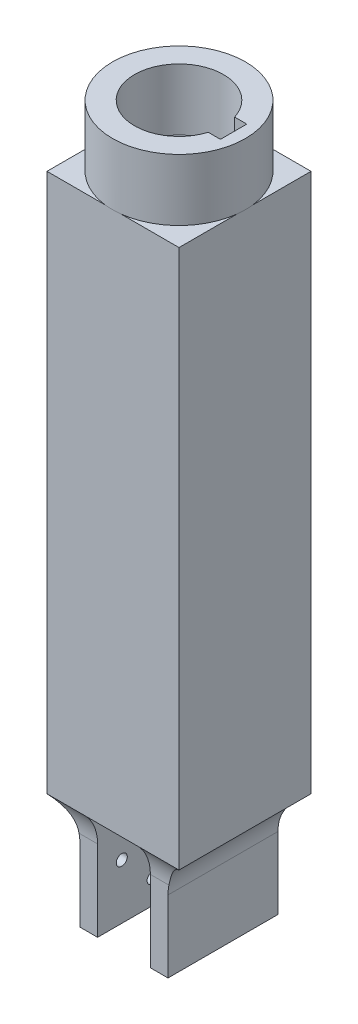
SolidWorks part; units mm, degrees
ref_plane "Front Plane" through (0, 0, 0) normal (0, 0, 1) x (1, 0, 0)
ref_plane "Top Plane" through (0, 0, 0) normal (0, 1, 0) x (1, 0, 0)
ref_plane "Right Plane" through (0, 0, 0) normal (1, 0, 0) x (0, 0, -1)
sketch "Sketch1" plane through (0, 0, 0) normal (0, 1, 0) x (1, 0, 0)
  line L1 (-15, -15) -> (15, -15)
  line L2 (-15, -15) -> (-15, 15)
  line L3 (-15, 15) -> (15, 15)
  line L4 (15, -15) -> (15, 15)
  line L5 (-15, -15) -> (15, 15) construction
  line L6 (-15, 15) -> (15, -15) construction
  point P0 (0, 0)
  dimension "D1" = 30
  dimension "D2" = 30
extrude "Boss-Extrude1" add sketch "Sketch1" along normal blind 122.5
sketch "Sketch2" plane through (0, 0, 0) normal (0, -1, 0) x (1, 0, 0)
  line L0 (-15, 15) -> (15, 15) construction
  line L1 (0, 0) -> (0, 15) construction
  line L6 (-15, -15) -> (-15, 15) construction
  line L7 (6, -12.5) -> (10, 12.5) construction
  line L8 (-6, 12.5) -> (-10, -12.5) construction
  line L9 (-6, -12.5) -> (-10, 12.5) construction
  line L10 (-10, -12.5) -> (-10, 12.5)
  line L11 (-6, 12.5) -> (-10, 12.5)
  line L12 (-6, -12.5) -> (-6, 12.5)
  line L13 (-6, -12.5) -> (-10, -12.5)
  line L14 (6, 12.5) -> (10, -12.5) construction
  line L15 (6, -12.5) -> (10, -12.5)
  line L16 (6, -12.5) -> (6, 12.5)
  line L17 (6, 12.5) -> (10, 12.5)
  line L18 (10, -12.5) -> (10, 12.5)
  point P15 (8, 0)
  point P23 (-8, 0)
  dimension "D1" = 4
  dimension "D2" = 25
  dimension "D4" = 5
  dimension "D5" = 2.5
extrude "Boss-Extrude2" add sketch "Sketch2" along normal blind 25
sketch "Sketch3" plane through (0, 122.5, 0) normal (0, 1, 0) x (1, 0, 0)
  line L8 (12, -12) -> (12, 12)
  line L9 (12, 12) -> (-12, 12)
  line L10 (-12, 12) -> (-12, -12)
  line L11 (-12, -12) -> (12, -12)
  line L12 (12, -12) -> (12, 12)
  line L13 (12, 12) -> (-12, 12)
  line L14 (-12, 12) -> (-12, -12)
  line L15 (-12, -12) -> (12, -12)
  dimension "D1" = 3
extrude "Cut-Extrude1" cut sketch "Sketch3" against normal blind 110
sketch "Sketch5" plane through (0, 122.5, 0) normal (0, 1, 0) x (1, 0, 0)
  line L5 (-15, -15) -> (15, 15) construction
  line L6 (-15, 15) -> (15, -15) construction
  line L11 (-12, -12) -> (12, -12)
  line L12 (-12, -12) -> (-12, 12)
  line L13 (-12, 12) -> (12, 12)
  line L14 (12, -12) -> (12, 12)
  line L15 (-12, -12) -> (12, 12) construction
  line L16 (-12, 12) -> (12, -12) construction
  point P0 (0, 0)
  point P7 (0, 0)
extrude "Boss-Extrude4" add sketch "Sketch5" against normal blind 4
sketch "Sketch4" plane through (0, 122.5, 0) normal (0, 1, 0) x (1, 0, 0)
  line L1 (12.4127, -2.9969) -> (12.4127, 2.9969)
  line L2 (12.4127, 2.9969) -> (9.6451, 2.9969)
  line L4 (12.4127, -2.9969) -> (9.6451, -2.9969)
  circle A1 centre (0, 0) radius 15.1
  arc A2 (9.6451, 2.9969) -> (9.6451, -2.9969) centre (0, 0) ccw
  point P7 (12.4127, 0)
  dimension "D1" = 20.2
  dimension "D2" = 5.9938
extrude "Boss-Extrude3" add sketch "Sketch4" along normal blind 14
sketch "Sketch7" plane through (0, 122.5, 0) normal (0, 1, 0) x (1, 0, 0)
  line L4 (12.4127, 2.9969) -> (12.4127, -2.9969)
  line L5 (12.4127, -2.9969) -> (9.6451, -2.9969)
  line L6 (9.6451, -2.9969) -> (9.6451, 2.9969)
  line L7 (9.6451, 2.9969) -> (12.4127, 2.9969)
extrude "Cut-Extrude3" cut sketch "Sketch7" against normal blind 4
sketch "Sketch8" plane through (-10, 0, 0) normal (-1, 0, 0) x (0, 0, 1)
  line L0 (-12.5, -25) -> (-12.5, 0) construction
  line L1 (12.5, -25) -> (-12.5, -25) construction
  circle A0 centre (0, -12.5) radius 7 construction
  circle A1 centre (0, -5.5) radius 1.25
  circle A2 centre (7, -12.5) radius 1.25
  circle A3 centre (0, -19.5) radius 1.25
  circle A4 centre (-7, -12.5) radius 1.25
  circle A5 centre (0, -12.5) radius 1.5
  point P13 (0, -12.5)
  dimension "D1" = 14
  dimension "D2" = 2.5
  dimension "D4" = 14
  dimension "D5" = 7
  dimension "D6" = 12.5
  dimension "D7" = 12.5
  dimension "D8" = 3
  dimension "D3" = 4
sketch "Sketch12" plane through (0, 122.5, 0) normal (0, 1, 0) x (1, 0, 0)
  circle A0 centre (0, 0) radius 2.1
  dimension "D1" = 4.2
extrude "Cut-Extrude6" cut sketch "Sketch12" against normal through all
sketch "Sketch13" plane through (0, 0, 0) normal (0, -1, 0) x (1, 0, 0)
  line L0 (-4.5, 11) -> (4.5, 11)
  line L1 (4.5, 11) -> (4.5, -11)
  line L2 (4.5, -11) -> (-4.5, -11)
  line L3 (-4.5, -11) -> (-4.5, 11)
  point P3 (0, 11)
  point P6 (4.5, 0)
  dimension "D1" = 9
  dimension "D2" = 22
extrude "Cut-Extrude7" cut sketch "Sketch13" against normal blind 20
extrude "Cut-Extrude4" cut sketch "Sketch8" against normal blind 4
fillet "Fillet1" radius 10 6 edges at (-8, 0, 12.5) (8, 0, 12.5) (8, 0, -12.5) (-8, 0, -12.5) (10, 0, 0) (-10, 0, 0)
